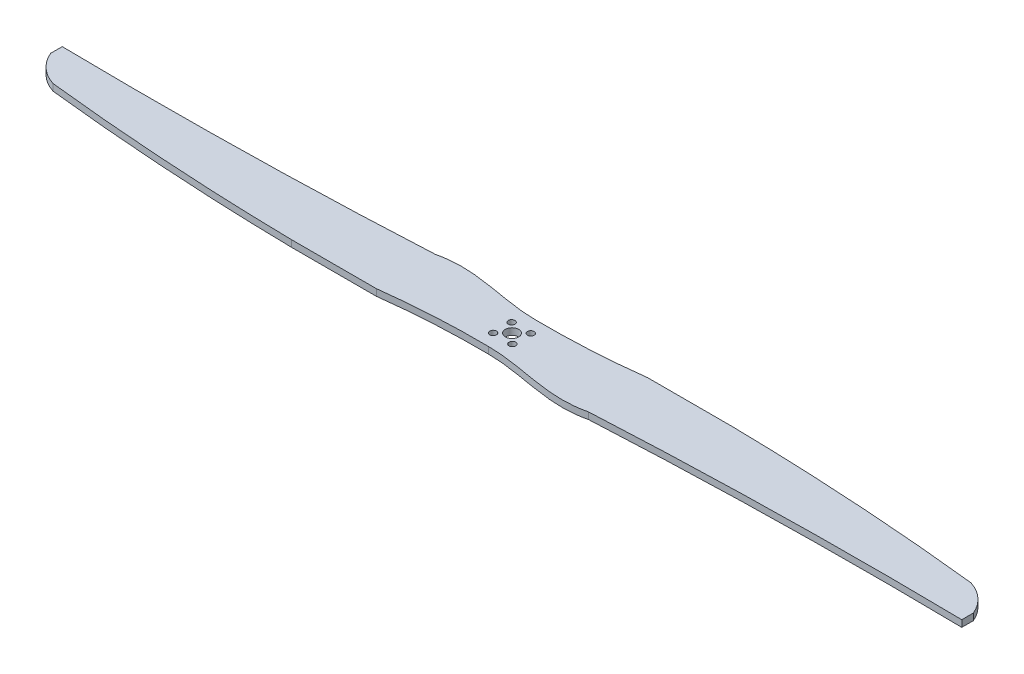
SolidWorks part; units mm, degrees
material "Hexcel AS4C (3000 Filaments)"
ref_plane "Front Plane" through (0, 0, 0) normal (0, 0, 1) x (1, 0, 0)
ref_plane "Top Plane" through (0, 0, 0) normal (0, 1, 0) x (1, 0, 0)
ref_plane "Right Plane" through (0, 0, 0) normal (1, 0, 0) x (0, 0, -1)
ref_axis "Axis1" through (0, 0.825, 0) along (0, -1, 0)
sketch "Sketch1" plane through (0, 0, 0) normal (0, 1, 0) x (1, 0, 0)
  line L0 (0, 0) -> (0, 17.5)
  line L1 (0, 0) -> (355.6, 0)
  line L2 (0, 17.5) -> (80, 17.5)
  line L3 (80, 17.5) -> (80, 22)
  line L4 (80, 17.5) -> (335, 17.5)
  line L5 (335, 17.5) -> (335, 10)
  line L6 (80, 17.5) -> (207.5, 17.5)
  line L7 (207.5, 17.5) -> (207.5, 22)
  line L8 (207.5, 22) -> (80, 22)
  line L9 (0, 0) -> (0, -17.5)
  line L10 (0, -17.5) -> (0, -22.5)
  line L11 (0, -22.5) -> (40, -22.5)
  line L12 (0, -20) -> (25, -20)
  line L13 (355.6, 0) -> (355.6, -17.5)
  circle A0 centre (0, 0) radius 5
  circle A1 centre (0, 0) radius 10
  arc A3 (80, 22) -> (0, 17.5) centre (7.2096, 602.6897) cw
  arc A4 (80, -22.5) -> (355.6, -17.5) centre (289.2923, -3960.6572) cw
  circle A5 centre (7.2096, 6.9297) radius 2.5
  circle A6 centre (7.2096, -6.9297) radius 2.5
  arc A7 (355.6, -8.75) -> (335, 10) centre (325.0757, -21.5947) ccw
  spline S0 degree 2 poles (335, 10) (207.7506, 23.9961) (80, 22) knots 0 0 0 1 1 1
  spline S1 degree 3 poles (0, -17.5) (26.9441, -17.5326) (52.6197, -29.066) (80, -22.5) knots 0 0 0 0 1 1 1 1
  dimension "D3" = 10
  dimension "D4" = 20
  dimension "D1" = 17.5
  dimension "D2" = 355.6
  dimension "D5" = 80
  dimension "D6" = 4.5
  dimension "D7" = 255
  dimension "D8" = 7.5
  dimension "D9" = 17.5
  dimension "D10" = 5
extrude "Boss-Extrude1" add sketch "Sketch1" along normal blind 2.5 and the other way blind 2.5 contours A5 A1 L0 A0 L1 | A6 A1 L1 A0 L9 | S0 L4 L2 A3 L0 A1 A5 L1 | L3 A3 L2 | L7 S0 L8 L3 L4 | L9 S1 A4 L13 L1 A1 A6 | L4 S0 L7 region at (4.679, 0, -4.7256) region at (4.679, 0, 4.7256) region at (165.6065, 0, -8.401) region at (170.0826, 0, 9.7899) region at (62.2629, 0, -18.8558) region at (139.2074, 0, -19.584) region at (222.388, 0, -18.3616)
pattern_circular "CirPattern1" count 2 over 360 about axis through (0, -2.5, 0) along (0, 1, 0) of "Boss-Extrude1"
